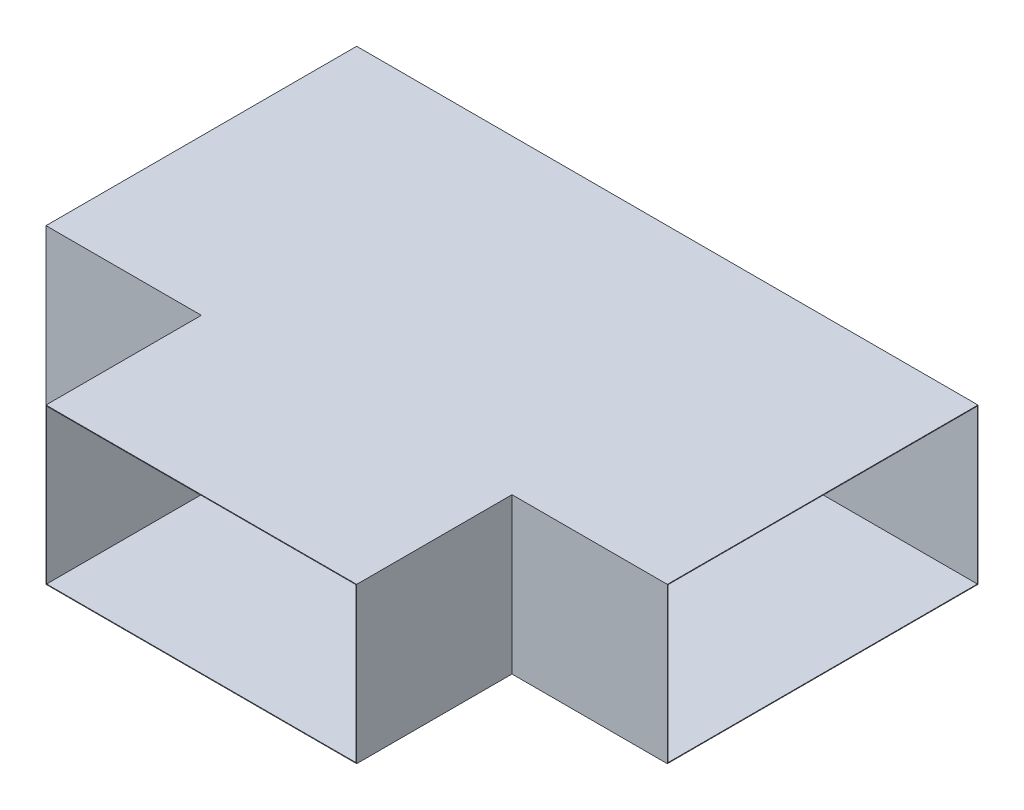
SolidWorks part; units mm, degrees
material "Plain Carbon Steel"
ref_plane "Front Plane" through (0, 0, 0) normal (0, 0, 1) x (1, 0, 0)
ref_plane "Top Plane" through (0, 0, 0) normal (0, 1, 0) x (1, 0, 0)
ref_plane "Right Plane" through (0, 0, 0) normal (1, 0, 0) x (0, 0, -1)
sketch "Sketch1" plane through (0, 0, 0) normal (1, 0, 0) x (0, 0, -1)
  line L0 (-500, 250) -> (500, -250) construction
  line L1 (-500, 250) -> (500, 250)
  line L2 (-500, 250) -> (-500, -250)
  line L3 (-500, -250) -> (500, -250)
  line L4 (500, 250) -> (500, -250)
  line L5 (-500, -250) -> (500, 250) construction
  dimension "Width" = 1000
  dimension "Height" = 500
extrude "Extrude-Thin1" add sketch "Sketch1" along normal mid plane 2000 thin thin type one direction reverse wall 2
sketch "Sketch2" plane through (0, -250, 500) normal (0, 0, -1) x (1, 0, 0)
  line L1 (-500, 0) -> (500, 0)
  line L2 (-500, 0) -> (-500, -500)
  line L3 (-500, -500) -> (500, -500)
  line L4 (500, 0) -> (500, -500)
  line L6 (-500, 0) -> (500, -500) construction
  line L7 (-500, -500) -> (500, 0) construction
  dimension "Width" = 1000
  dimension "Height" = 500
extrude "Extrude-Thin2" add sketch "Sketch2" against normal blind 500 thin thin type one direction reverse wall 2
sketch "Sketch3" plane through (0, -750, 1000) normal (0, 0, -1) x (1, 0, 0)
  line L0 (-498, -502) -> (-498, -998) construction
  line L1 (-498, -998) -> (498, -998) construction
  line L2 (498, -998) -> (498, -502) construction
  line L3 (498, -502) -> (-498, -502) construction
  line L4 (-498, -502) -> (-498, -998)
  line L5 (-498, -998) -> (498, -998)
  line L6 (498, -998) -> (498, -502)
  line L7 (498, -502) -> (-498, -502)
extrude "Cut-Extrude1" cut sketch "Sketch3" along normal up to next
sketch "Sketch4" plane through (0, 0, 0) normal (0, 1, 0) x (1, 0, 0)
  line L0 (498, -1000) -> (-498, -1000) construction
  line L3 (1000, -498) -> (1000, 498) construction
  line L4 (-1000, -498) -> (-1000, 498) construction
  point P0 (1000, 0)
  point P1 (-1000, 0)
  point P2 (0, -1000)
  point P3 (0, 0)
other "CPoint1" parameters "Diameter"=10, "StubLength"=500
ref_axis "Axis1" through (1010, 0, 0) along (-1, 0, 0)
other "CPoint2" parameters "Diameter"=10, "StubLength"=500
ref_axis "Axis2" through (-1010, 0, 0) along (1, 0, 0)
other "CPoint3" parameters "Diameter"=10, "StubLength"=500
ref_axis "Axis3" through (0, 0, 1010) along (0, 0, -1)
other "RPoint1"
equation "\"Thickness@Extrude-Thin2\" = \"Thickness@Extrude-Thin1\""
equation "\"D1@Extrude-Thin1\"=2 * \"Width@Sketch1\""
equation "\"D1@Extrude-Thin2\"=0.5 * \"Width@Sketch1\""
